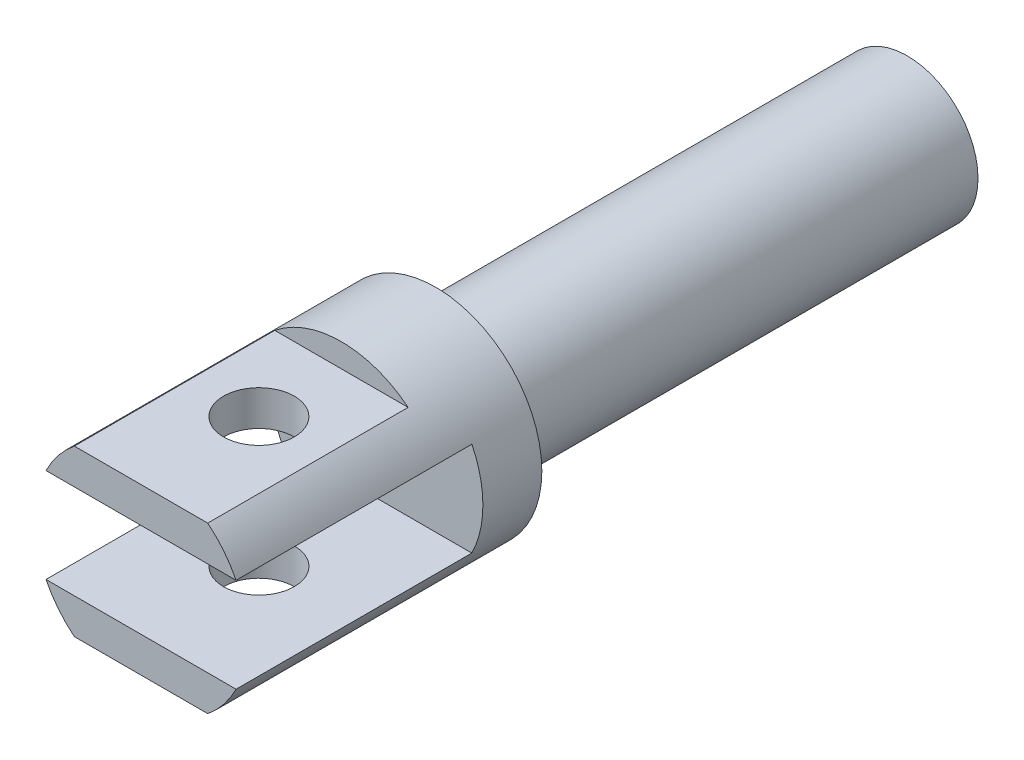
SolidWorks part; units mm, degrees
material "1.0545 (S355N)"
ref_plane "Płaszczyzna przednia" through (0, 0, 0) normal (0, 0, 1) x (1, 0, 0)
ref_plane "Płaszczyzna górna" through (0, 0, 0) normal (0, 1, 0) x (1, 0, 0)
ref_plane "Płaszczyzna prawa" through (0, 0, 0) normal (1, 0, 0) x (0, 0, -1)
sketch "Szkic1" plane through (0, 0, 0) normal (0, 1, 0) x (1, 0, 0)
  line L0 (0, -44.41) -> (0, 49.6533) construction
  line L1 (-9, 0) -> (9, 0)
  line L2 (-9, 0) -> (-9, -25)
  line L3 (-9, -25) -> (9, -25)
  line L4 (9, 0) -> (9, -25)
  line L5 (-6, 40) -> (6, 40)
  line L6 (-6, 40) -> (-6, 0)
  line L7 (-6, 0) -> (6, 0)
  line L8 (6, 40) -> (6, 0)
  point P8 (0, 0)
  point P9 (0, 0)
  dimension "D1" = 12
  dimension "D2" = 18
  dimension "D3" = 40
  dimension "D4" = 25
revolve "Obrót1" add sketch "Szkic1" angle 360 about L0 region at (4.5, 0, 12.5) region at (3, 0, -20)
sketch "Szkic2" plane through (0, 0, 25) normal (0, 0, 1) x (1, 0, 0)
  line L1 (-9, 4) -> (9, 4)
  line L2 (-9, 4) -> (-9, -4)
  line L3 (-9, -4) -> (9, -4)
  line L4 (9, 4) -> (9, -4)
  circle A2 centre (0, 0) radius 9 construction
  point P4 (0, 4)
  point P6 (-9, 0)
  point P7 (9, 0)
  dimension "D1" = 8
extrude "Wytnij-wyciągnięcie1" cut sketch "Szkic2" against normal blind 20
sketch "Szkic3" plane through (0, 0, 0) normal (0, 1, 0) x (1, 0, 0)
  line L0 (-8.0623, -5) -> (8.0623, -5) construction
  line L1 (-8.0623, -5) -> (-8.0623, -25) construction
  line L2 (8.0623, -25) -> (-8.0623, -25)
  line L3 (8.0623, -25) -> (8.0623, -8)
  line L4 (8.0623, -8) -> (-8.0623, -8)
  line L5 (-8.0623, -25) -> (-8.0623, -8)
  circle A0 centre (0, -15) radius 3
  dimension "D2" = 6
  dimension "D3" = 17
  dimension "D1" = 10
extrude "Wytnij-wyciągnięcie2" cut sketch "Szkic3" against normal through all both and the other way through all contours A0
extrude "Wytnij-wyciągnięcie3" cut sketch "Szkic3<4>" along normal through all from offset 7
sketch "Szkic3<4>" plane through (0, 0, 0) normal (0, 1, 0) x (1, 0, 0) same geometry as "Szkic3"
mirror "Lustro1" about plane through (0, 0, 0) normal (0, 1, 0) of "Wytnij-wyciągnięcie3"
equation "\"D1@Wytnij-wyciągnięcie1\"=\"D4@Szkic1\" - 5"
